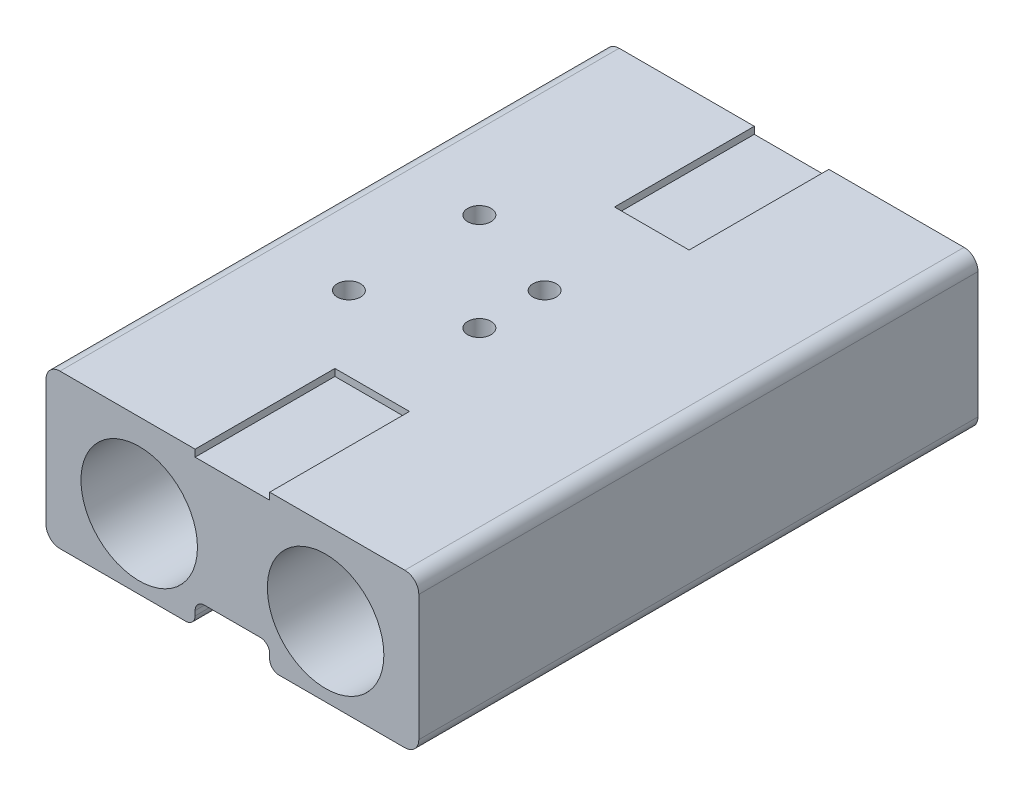
SolidWorks part; units mm, degrees
ref_plane "前视基准面" through (0, 0, 0) normal (0, 0, 1) x (1, 0, 0)
ref_plane "上视基准面" through (0, 0, 0) normal (0, 1, 0) x (1, 0, 0)
ref_plane "右视基准面" through (0, 0, 0) normal (1, 0, 0) x (0, 0, -1)
sketch "草图1" plane through (0, 0, 0) normal (0, 0, 1) x (1, 0, 0)
  line L2 (-20, -7.5) -> (-20, 9)
  line L3 (-20, 9) -> (20, 9)
  line L4 (20, -7.5) -> (20, 9)
  line L7 (0, -7.5) -> (-20, -7.5)
  line L8 (0, -7.5) -> (20, -7.5)
  circle A0 centre (-10, 0) radius 3.5
  circle A2 centre (10, 0) radius 3.5
  point P0 (0, 0)
extrude "凸台-拉伸1" add sketch "草图1" along normal blind 60 contours L4 L3 L2 A2 A0 region at (0, 0.849, 0)
fillet "圆角1" radius 1.5 4 edges at (-20, 9, 30) (20, 9, 30) (20, -7.5, 30) (-20, -7.5, 30)
sketch "草图2" plane through (0, 0, 60) normal (0, 0, 1) x (1, 0, 0)
  circle A0 centre (10, 0) radius 6.25
  circle A1 centre (-10, 0) radius 6.25
extrude "切除-拉伸1" cut sketch "草图2" against normal blind 20
sketch "草图3" plane through (0, 0, 0) normal (0, 0, -1) x (-1, 0, 0)
  circle A0 centre (-10, 0) radius 6.25
  circle A1 centre (10, 0) radius 6.25
extrude "切除-拉伸2" cut sketch "草图3" against normal blind 20
sketch "草图5" plane through (0, 0, 0) normal (0, 0, -1) x (-1, 0, 0)
  line L7 (0, -5) -> (4, -5)
  line L8 (4, -5) -> (4, -9)
  line L9 (4, -9) -> (-4, -9)
  line L10 (-4, -9) -> (-4, -5)
  line L11 (-4, -5) -> (0, -5)
  line L12 (-4, 8.25) -> (4, 8.25)
  line L13 (4, 8.25) -> (4, 9)
  line L14 (18.5, 9) -> (-18.5, 9) construction
  line L15 (4, 9) -> (-4, 9)
  line L16 (-4, 9) -> (-4, 8.25)
extrude "切除-拉伸4" cut sketch "草图5" against normal blind 62
fillet "圆角2" radius 1 4 edges at (-4, -5, 30) (4, -5, 30) (-4, -7.5, 30) (4, -7.5, 30)
sketch "草图7" plane through (0, 9, 0) normal (0, 1, 0) x (1, 0, 0)
  line L0 (-4, -60) -> (-4, 0) construction
  line L10 (4, -15) -> (-4, -15)
  line L11 (4, -15) -> (4, -45)
  line L12 (4, -45) -> (-4, -45)
  line L13 (-4, -15) -> (-4, -45)
extrude "凸台-拉伸2" add sketch "草图7" against normal blind 2
sketch "草图6" plane through (0, 9, 0) normal (0, 1, 0) x (1, 0, 0)
  circle A0 centre (0, -26.5) radius 1.25
  circle A1 centre (0, -33.5) radius 1.25
extrude "切除-拉伸5" cut sketch "草图6" against normal blind 62
sketch "草图8" plane through (0, 9, 0) normal (0, 1, 0) x (1, 0, 0)
  circle A0 centre (-10.5, -23) radius 1.25
  circle A1 centre (-10.5, -37) radius 1.25
extrude "切除-拉伸6" cut sketch "草图8" against normal blind 5
sketch "草图9" plane through (0, -5, 0) normal (0, -1, 0) x (1, 0, 0)
  line L1 (2.4749, 28.9749) -> (2.4749, 31.0251)
  line L3 (-2.4749, 28.9749) -> (-2.4749, 31.0251)
  arc A0 (2.4749, 31.0251) -> (-2.4749, 31.0251) centre (0, 33.5) ccw
  arc A1 (-2.4749, 28.9749) -> (2.4749, 28.9749) centre (0, 26.5) ccw
extrude "切除-拉伸9" cut sketch "草图9" against normal blind 8 and the other way blind 5
